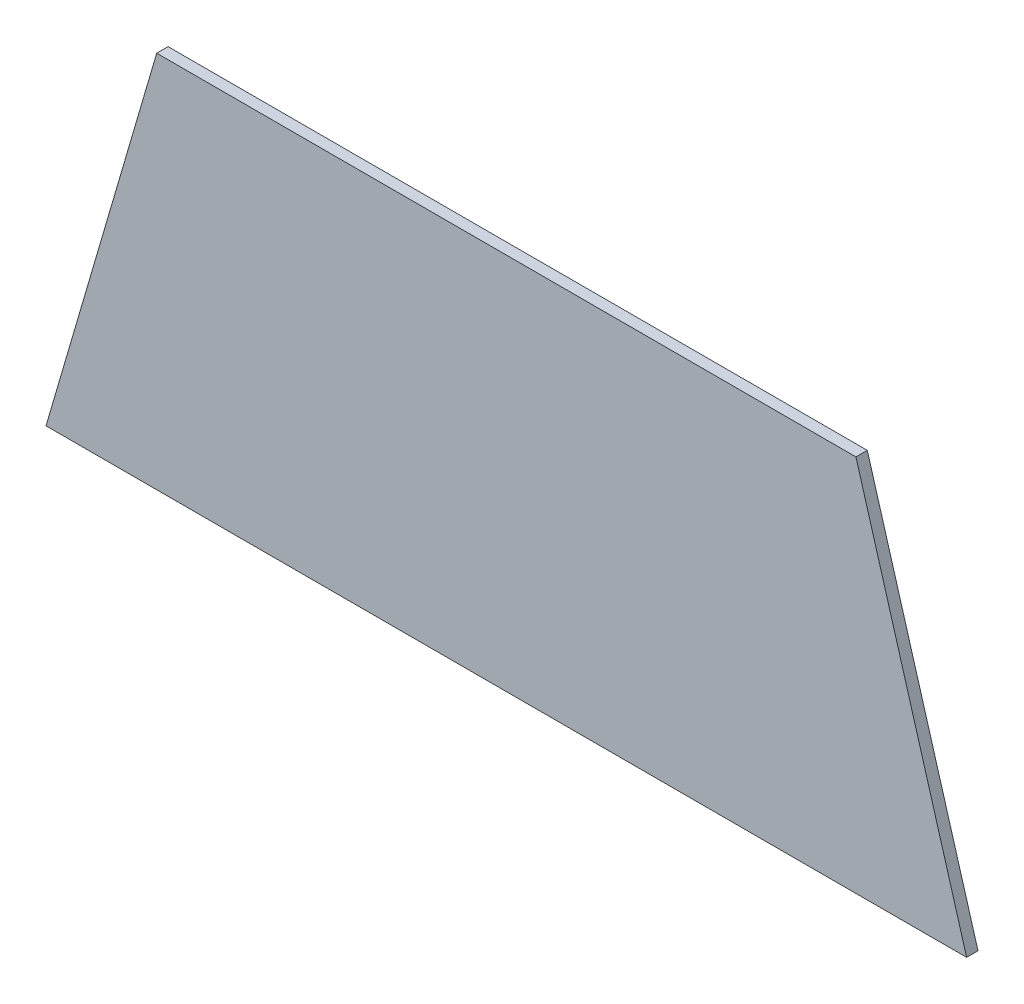
SolidWorks part; units mm, degrees
ref_plane "Front Plane" through (0, 0, 0) normal (0, 0, 1) x (1, 0, 0)
ref_plane "Top Plane" through (0, 0, 0) normal (0, 1, 0) x (1, 0, 0)
ref_plane "Right Plane" through (0, 0, 0) normal (1, 0, 0) x (0, 0, -1)
sketch "Sketch1" plane through (0, 0, 0) normal (0, 0, 1) x (1, 0, 0)
  line L0 (1.5, 0) -> (245, 0)
  line L3 (149.129, 0) -> (149.129, 100) construction
  line L5 (1.5, 0) -> (30.7799, 100)
  line L6 (245, 0) -> (215.7201, 100)
  line L7 (30.7799, 100) -> (215.7201, 100)
extrude "Boss-Extrude1" add sketch "Sketch1" along normal blind 3 and the other way blind 0.0067
